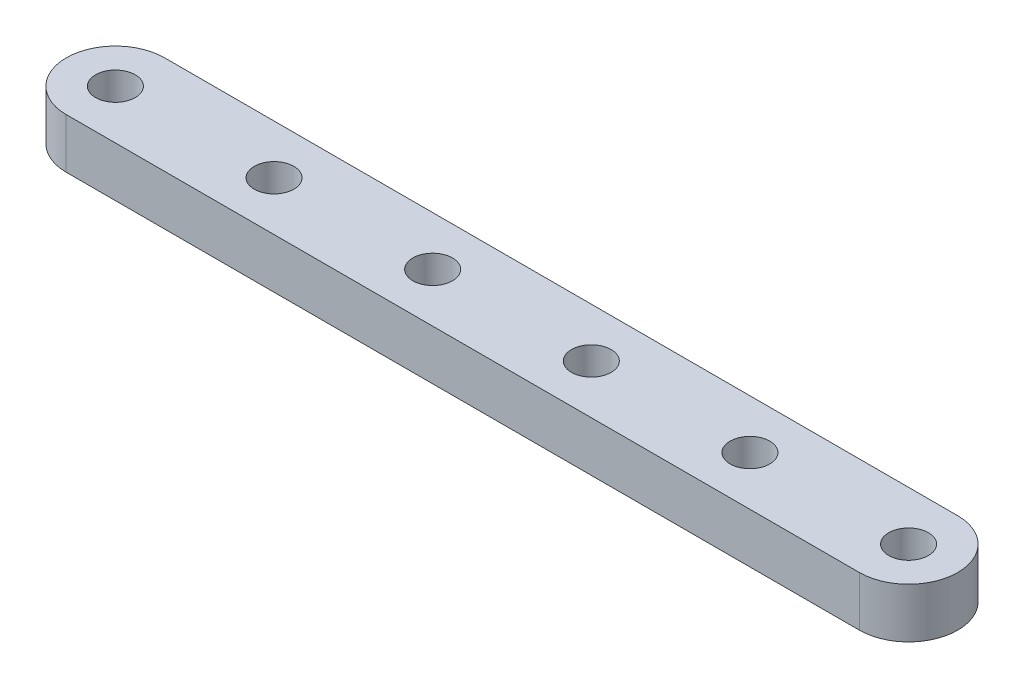
SolidWorks part; units mm, degrees
ref_plane "Front Plane" through (0, 0, 0) normal (0, 0, 1) x (1, 0, 0)
ref_plane "Top Plane" through (0, 0, 0) normal (0, 1, 0) x (1, 0, 0)
ref_plane "Right Plane" through (0, 0, 0) normal (1, 0, 0) x (0, 0, -1)
sketch "Sketch1" plane through (0, 0, 0) normal (0, 1, 0) x (1, 0, 0)
  line L0 (24.13, 0) -> (-24.13, 0) construction
  line L1 (24.13, -8.89) -> (-24.13, -8.89)
  line L2 (24.13, 8.89) -> (-24.13, 8.89)
  arc A0 (24.13, -8.89) -> (24.13, 8.89) centre (24.13, 0) ccw
  arc A1 (-24.13, 8.89) -> (-24.13, -8.89) centre (-24.13, 0) ccw
  point P2 (0, 0)
  point P8 (-33.02, 0)
  point P9 (33.02, 0)
  dimension "D1" = 17.78
  dimension "D2" = 66.04
extrude "Boss-Extrude1" add sketch "Sketch1" along normal blind 2
sketch "Sketch2" plane through (0, 2, 0) normal (0, 1, 0) x (1, 0, 0)
  line L0 (-33.02, 0) -> (33.02, 0) construction
  line L1 (-25.4, 3.1496) -> (25.4, 3.1496)
  line L2 (-24.13, -8.89) -> (24.13, -8.89) construction
  line L3 (25.4, 1.524) -> (-25.4, 1.524)
  line L4 (25.4, 1.524) -> (25.4, -1.524)
  line L5 (25.4, -1.524) -> (-25.4, -1.524)
  line L6 (-25.4, 1.524) -> (-25.4, -1.524)
  line L7 (25.4, 1.524) -> (-25.4, -1.524) construction
  line L8 (25.4, -1.524) -> (-25.4, 1.524) construction
  line L9 (-25.4, -3.1496) -> (25.4, -3.1496)
  arc A0 (-24.13, 8.89) -> (-24.13, -8.89) centre (-24.13, 0) ccw construction
  arc A1 (24.13, -8.89) -> (24.13, 8.89) centre (24.13, 0) ccw construction
  circle A2 centre (-25.4, 0) radius 3.1496
  circle A3 centre (-15.24, 0) radius 3.1496
  circle A4 centre (-5.08, 0) radius 3.1496
  circle A5 centre (5.08, 0) radius 3.1496
  circle A6 centre (15.24, 0) radius 3.1496
  circle A7 centre (25.4, 0) radius 3.1496
  circle A8 centre (-25.4, 0) radius 1.27
  circle A9 centre (-15.24, 0) radius 1.27
  circle A10 centre (-5.08, 0) radius 1.27
  circle A11 centre (5.08, 0) radius 1.27
  circle A12 centre (15.24, 0) radius 1.27
  circle A13 centre (25.4, 0) radius 1.27
  point P10 (0, 0)
  point P30 (0, -8.89)
  dimension "D1" = 6.2992
  dimension "D3" = 6
  dimension "D7" = 2.54
  dimension "D2" = 7.62
  dimension "D4" = 8.89
  dimension "D5" = 7.366
  dimension "D6" = 50.8
  dimension "D8" = 6
extrude "Boss-Extrude2" add sketch "Sketch2" along normal blind 1.2 contours A3 L1 A2 L3 | A4 L1 A3 L3 | A5 L1 A4 L3 | A6 L1 A5 L3 | A7 L1 A6 L3 | A7 L5 A6 L9 | A6 L5 A5 L9 | A5 L5 A4 L9 | A4 L5 A3 L9 | A3 L5 A2 L9 | A8 L6 L3 A2 L5 | A8 L6 L5 A2 L3 | A3 L3 A2 L5 | L5 A3 L3 A9 | A3 L5 | L3 A3 | A4 L3 A3 L5 | A4 L5 | L3 A4 | L5 A4 L3 A10 | L5 A5 L3 A11 | A5 L5 | A5 L3 A4 L5 | L3 A5 | A6 L3 A5 L5 | A6 L5 | L5 A6 L3 A12 | L3 A6 | A7 L3 A6 L5 | A13 L4 L5 A7 L3 | A13 L4 L3 A7 L5 region at (-23.8439, 2, -2.6386) region at (-20.32, 2, -2.4283) region at (-10.16, 2, -2.4283) region at (-15.24, 2, -2.1912) region at (-20.32, 2, 2.4283) region at (-23.5172, 2, 0) region at (-20.32, 2, 0) region at (0, 2, -2.4283) region at (-5.08, 2, -2.1912) region at (-12.2581, 2, -0.7695) region at (-10.16, 2, 0) region at (-10.16, 2, 2.4283) region at (-15.24, 2, 2.1912) region at (10.16, 2, -2.4283) region at (5.08, 2, -2.1912) region at (-2.0981, 2, -0.7695) region at (0, 2, 0) region at (0, 2, 2.4283) region at (-5.08, 2, 2.1912) region at (20.32, 2, -2.4283) region at (15.24, 2, -2.1912) region at (8.0619, 2, -0.7695) region at (10.16, 2, 0) region at (10.16, 2, 2.4283) region at (5.08, 2, 2.1912) region at (27.566, 2, -2.166) region at (18.2219, 2, -0.7695) region at (20.32, 2, 0) region at (20.32, 2, 2.4283) region at (15.24, 2, 2.1912) region at (23.5172, 2, 0)
extrude "Cut-Extrude1" cut sketch "Sketch2<3>" against normal through all both and the other way through all contours A8 | A9 | A10 | A11 | A12 | A13
sketch "Sketch2<3>" plane through (0, 2, 0) normal (0, 1, 0) x (1, 0, 0) same geometry as "Sketch2"
sketch "Sketch3" plane through (0, 2, 0) normal (0, 1, 0) x (1, 0, 0)
  line L0 (-25.4, -3.1496) -> (25.4, -3.1496) construction
  line L1 (-25.4, 3.1496) -> (25.4, 3.1496) construction
  line L2 (-25.4, -3.1496) -> (25.4, -3.1496)
  line L3 (-25.4, 3.1496) -> (25.4, 3.1496)
  line L6 (24.13, 8.89) -> (-24.13, 8.89)
  line L7 (-24.13, -8.89) -> (24.13, -8.89)
  line L8 (24.13, 8.89) -> (-24.13, 8.89)
  line L9 (-24.13, -8.89) -> (24.13, -8.89)
  arc A0 (-25.4, 3.1496) -> (-25.4, -3.1496) centre (-25.4, 0) ccw construction
  arc A1 (-25.4, 3.1496) -> (-25.4, -3.1496) centre (-25.4, 0) ccw
  arc A2 (25.4, -3.1496) -> (25.4, 3.1496) centre (25.4, 0) ccw construction
  arc A3 (25.4, -3.1496) -> (25.4, 3.1496) centre (25.4, 0) ccw
  arc A6 (24.13, -8.89) -> (24.13, 8.89) centre (24.13, 0) ccw
  arc A7 (-24.13, 8.89) -> (-24.13, -8.89) centre (-24.13, 0) ccw
  arc A8 (24.13, -8.89) -> (24.13, 8.89) centre (24.13, 0) ccw
  arc A9 (-24.13, 8.89) -> (-24.13, -8.89) centre (-24.13, 0) ccw
  dimension "D1" = 0
extrude "Cut-Extrude2" cut sketch "Sketch3" against normal through all
